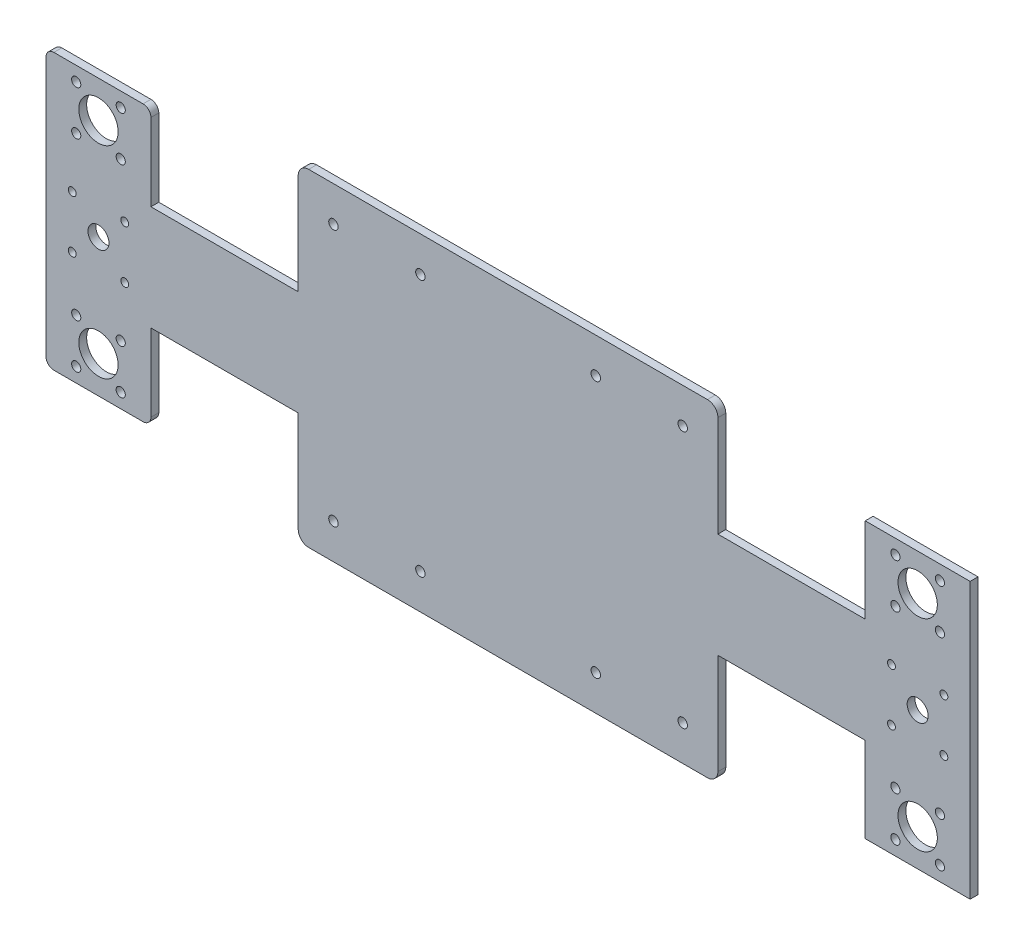
SolidWorks part; units mm, degrees
ref_plane "정면" through (0, 0, 0) normal (0, 0, 1) x (1, 0, 0)
ref_plane "윗면" through (0, 0, 0) normal (0, 1, 0) x (1, 0, 0)
ref_plane "우측면" through (0, 0, 0) normal (1, 0, 0) x (0, 0, -1)
sketch "스케치1" plane through (0, 0, 0) normal (0, 0, 1) x (1, 0, 0)
  line L0 (0, 20) -> (0, -20) construction
  line L1 (-156.15, -20) -> (156.15, -20)
  line L2 (-156.15, -20) -> (-156.15, 20)
  line L3 (-156.15, 20) -> (156.15, 20)
  line L4 (156.15, -20) -> (156.15, 20)
  line L5 (-156.15, -20) -> (156.15, 20) construction
  line L6 (-156.15, 20) -> (156.15, -20) construction
  line L7 (176.15, -20) -> (176.15, 20)
  line L8 (-176.15, -20) -> (-136.15, -20)
  line L9 (-176.15, -20) -> (-176.15, 20)
  line L10 (-176.15, 20) -> (-136.15, 20)
  line L11 (-136.15, -20) -> (-136.15, 20)
  line L12 (-176.15, -20) -> (-136.15, 20) construction
  line L13 (-176.15, 20) -> (-136.15, -20) construction
  line L14 (176.15, -20) -> (136.15, 20) construction
  line L15 (176.15, 20) -> (136.15, -20) construction
  line L16 (176.15, -20) -> (136.15, -20)
  line L17 (136.15, -20) -> (136.15, 20)
  line L18 (176.15, 20) -> (136.15, 20)
  line L19 (146.15, -10) -> (146.15, 10) construction
  line L20 (-166.15, -10) -> (-146.15, -10) construction
  line L21 (-166.15, -10) -> (-166.15, 10) construction
  line L22 (-166.15, 10) -> (-146.15, 10) construction
  line L23 (-146.15, -10) -> (-146.15, 10) construction
  line L24 (-166.15, -10) -> (-146.15, 10) construction
  line L25 (-166.15, 10) -> (-146.15, -10) construction
  line L26 (166.15, -10) -> (146.15, -10) construction
  line L27 (166.15, -10) -> (166.15, 10) construction
  line L28 (166.15, 10) -> (146.15, 10) construction
  circle A0 centre (-156.15, 0) radius 4
  circle A1 centre (156.15, 0) radius 4
  circle A2 centre (-166.15, 10) radius 1.5
  circle A3 centre (-146.15, 10) radius 1.5
  circle A4 centre (-166.15, -10) radius 1.5
  circle A5 centre (-146.15, -10) radius 1.5
  circle A6 centre (146.15, 10) radius 1.5
  circle A7 centre (166.15, 10) radius 1.5
  circle A8 centre (166.15, -10) radius 1.5
  circle A9 centre (146.15, -10) radius 1.5
  point P0 (0, 0)
  point P20 (156.15, 0)
  dimension "D3" = 8
  dimension "D5" = 3
  dimension "D1" = 312.3
  dimension "D4" = 40
  dimension "D6" = 20
extrude "보스-돌출1" add sketch "스케치1" along normal blind 3 contours L4 A1 L16 L7 L18 A7 A8 | L4 A1 L3 L17 L1 A9 A6 | L1 L17 L3 L11 | A0 L2 L10 L9 L8 A4 A2 | A0 L2 L1 L11 L3 A3 A5 region at (-145.8757, 0, 0) region at (-166.4243, 0, 0) region at (0, 0, 0) region at (145.8757, 0, 0) region at (166.4243, 0, 0)
fillet "필렛1" radius 7 4 edges at (-176.15, -20, 1.5) (-176.15, 20, 1.5) (176.15, -20, 1.5) (176.15, 20, 1.5)
sketch "스케치2" plane through (0, 0, 3) normal (0, 0, 1) x (1, 0, 0)
  line L0 (0, 49) -> (0, -49) construction
  line L1 (-80, -62.43) -> (80, -62.43)
  line L2 (-80, -62.43) -> (-80, 62.43)
  line L3 (-80, 62.43) -> (80, 62.43)
  line L4 (80, -62.43) -> (80, 62.43)
  line L5 (-80, -62.43) -> (80, 62.43) construction
  line L6 (-80, 62.43) -> (80, -62.43) construction
  line L7 (-66.575, -49) -> (66.575, -49)
  line L8 (-66.575, -49) -> (-66.575, 49)
  line L9 (-66.575, 49) -> (66.575, 49)
  line L10 (66.575, -49) -> (66.575, 49)
  line L11 (-66.575, -49) -> (66.575, 49) construction
  line L12 (-66.575, 49) -> (66.575, -49) construction
  line L13 (-33.425, -49) -> (33.425, -49)
  line L14 (-33.425, -49) -> (-33.425, 49)
  line L15 (-33.425, 49) -> (33.425, 49)
  line L16 (33.425, -49) -> (33.425, 49)
  line L17 (-33.425, -49) -> (33.425, 49) construction
  line L18 (-33.425, 49) -> (33.425, -49) construction
  circle A0 centre (-66.575, 49) radius 1.8
  circle A1 centre (-33.425, 49) radius 1.8
  circle A2 centre (-66.575, -49) radius 1.8
  circle A3 centre (-33.425, -49) radius 1.8
  circle A4 centre (33.425, -49) radius 1.8
  circle A5 centre (66.575, -49) radius 1.8
  circle A6 centre (66.575, 49) radius 1.8
  circle A7 centre (33.425, 49) radius 1.8
  point P0 (0, 0)
  point P6 (0, 0)
  point P11 (0, 0)
  line M9 (-169.15, -20) -> (169.15, -20)
  line M13 (169.15, 20) -> (-169.15, 20)
  dimension "D5" = 3.6
  dimension "D1" = 160
  dimension "D2" = 98
  dimension "D3" = 66.85
  dimension "D4" = 33.15
  dimension "D6" = 13.43
extrude "보스-돌출2" add sketch "스케치2" against normal blind 3 contours L15 A7 L9 A6 L10 L4 L3 L2 L8 A0 A1 M13 | L8 L2 M9 M13 | L10 A5 L7 A4 L13 A3 A2 L8 L2 L1 L4 M9 | L14 L8 M9 M13 | A1 L9 A0 L8 L14 M13 | L16 A7 L15 A1 L14 M13 | L16 L14 M9 M13 | L16 L10 M9 M13 | L9 A7 L16 L10 A6 M13 | L7 A5 L10 L16 A4 M9 | A3 L14 L8 A2 L7 M9 | L13 A4 L16 L14 A3 M9 region at (0, -50.0776, 3) region at (-73.2875, 0, 3) region at (0, 50.0776, 3) region at (-50, -34.4269, 3) region at (-50, 0, 3) region at (50, 0, 3) region at (50, -34.4269, 3) region at (-50, 34.4269, 3) region at (0, -34.4638, 3) region at (0, 0, 3) region at (50, 34.4269, 3) region at (0, 34.4638, 3)
fillet "필렛2" radius 4 4 edges at (-80, -62.43, 1.5) (80, -62.43, 1.5) (80, 62.43, 1.5) (-80, 62.43, 1.5)
sketch "스케치3" plane through (0, 0, 3) normal (0, 0, 1) x (1, 0, 0)
  line L0 (-176.15, -13) -> (-176.15, 13) construction
  line L1 (-176.15, -52.4706) -> (-136.15, -52.4706)
  line L2 (-176.15, -52.4706) -> (-176.15, 52.4706)
  line L3 (-176.15, 52.4706) -> (-136.15, 52.4706)
  line L4 (-136.15, -52.4706) -> (-136.15, 52.4706)
  line L5 (-176.15, -52.4706) -> (-136.15, 52.4706) construction
  line L6 (-176.15, 52.4706) -> (-136.15, -52.4706) construction
  line L7 (-176.15, 0) -> (-136.15, 0) construction
  line L8 (-164.6353, -30) -> (-164.6353, -46.9706)
  line L9 (-164.6353, 30) -> (-147.6647, 30) construction
  line L10 (-164.6353, 30) -> (-164.6353, 46.9706) construction
  line L11 (-164.6353, 46.9706) -> (-147.6647, 46.9706) construction
  line L12 (-147.6647, 30) -> (-147.6647, 46.9706) construction
  line L13 (-164.6353, 30) -> (-147.6647, 46.9706) construction
  line L14 (-164.6353, 46.9706) -> (-147.6647, 30) construction
  line L15 (-164.6353, -30) -> (-147.6647, -46.9706) construction
  line L16 (-164.6353, -46.9706) -> (-147.6647, -30) construction
  line L17 (-164.6353, -30) -> (-147.6647, -30)
  line L18 (-147.6647, -30) -> (-147.6647, -46.9706)
  line L19 (-164.6353, -46.9706) -> (-147.6647, -46.9706)
  line L20 (-156.15, 52.4706) -> (-156.15, -52.4706) construction
  line L21 (-80, 20) -> (-169.15, 20) construction
  circle A0 centre (-156.15, 0) radius 4
  circle A1 centre (-164.6353, 46.9706) radius 1.75
  circle A2 centre (-164.6353, -46.9706) radius 1.75
  circle A3 centre (-147.6647, 46.9706) radius 1.75
  circle A4 centre (-147.6647, -46.9706) radius 1.75
  circle A5 centre (-164.6353, 30) radius 1.75
  circle A6 centre (-164.6353, -30) radius 1.75
  circle A7 centre (-147.6647, 30) radius 1.75
  circle A8 centre (-147.6647, -30) radius 1.75
  circle A9 centre (-156.15, 38.4853) radius 7.5
  circle A10 centre (-156.15, -38.4853) radius 7.5
  circle A11 centre (-156.15, 38.4853) radius 12 construction
  point P11 (-156.15, 38.4853)
  point P20 (-156.15, -38.4853)
  line M24 (-80, 20) -> (-169.15, 20)
  arc M25 (-169.15, 20) -> (-176.15, 13) centre (-169.15, 13) ccw
  arc M27 (-176.15, -13) -> (-169.15, -20) centre (-169.15, -13) ccw
  line M28 (-169.15, -20) -> (-80, -20)
  dimension "D2" = 3.5
  dimension "D3" = 15
  dimension "D1" = 24
  dimension "D4" = 5.5
  dimension "D5" = 10
extrude "보스-돌출3" add sketch "스케치3" against normal blind 3 contours L4 L3 L2 A9 A7 A5 A3 A1 M24 M25 | L1 L4 L2 L17 A8 L18 A4 L19 A2 L8 A6 M28 M27 | L18 A8 L17 A6 L8 A2 L19 A4 A10 region at (-175.588, -32.7353, 3) region at (-175.588, 32.7353, 3) region at (-163.2281, -31.4071, 3)
fillet "필렛3" radius 3 4 edges at (-176.15, 52.4706, 1.5) (-136.15, 52.4706, 1.5) (-176.15, -52.4706, 1.5) (-136.15, -52.4706, 1.5)
mirror "대칭 복사1" about plane through (0, 0, 0) normal (1, 0, 0) of "보스-돌출3"
